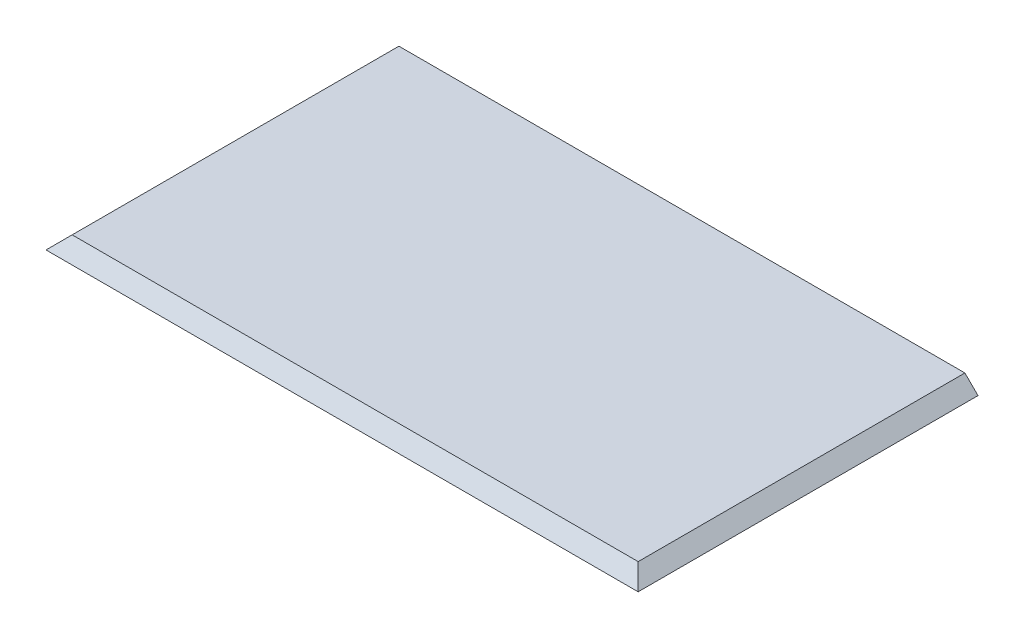
SolidWorks part; units mm, degrees
ref_plane "Front Plane" through (0, 0, 0) normal (0, 0, 1) x (1, 0, 0)
ref_plane "Top Plane" through (0, 0, 0) normal (0, 1, 0) x (1, 0, 0)
ref_plane "Right Plane" through (0, 0, 0) normal (1, 0, 0) x (0, 0, -1)
sketch "Sketch1" plane through (0, 0, 0) normal (0, 1, 0) x (1, 0, 0)
  line L1 (287.5, -165) -> (-287.5, -165)
  line L2 (287.5, -165) -> (287.5, 165)
  line L3 (287.5, 165) -> (-287.5, 165)
  line L4 (-287.5, -165) -> (-287.5, 165)
  line L5 (287.5, -165) -> (-287.5, 165) construction
  line L6 (287.5, 165) -> (-287.5, -165) construction
  point P1 (0, 0)
  dimension "D1" = 330
  dimension "D2" = 575
extrude "Boss-Extrude1" add sketch "Sketch1" along normal blind 12.7
chamfer "Chamfer1" distance 12.7 angle 45 3 edges at (287.5, 12.7, 0) (0, 12.7, 165) (-287.5, 12.7, 0)
